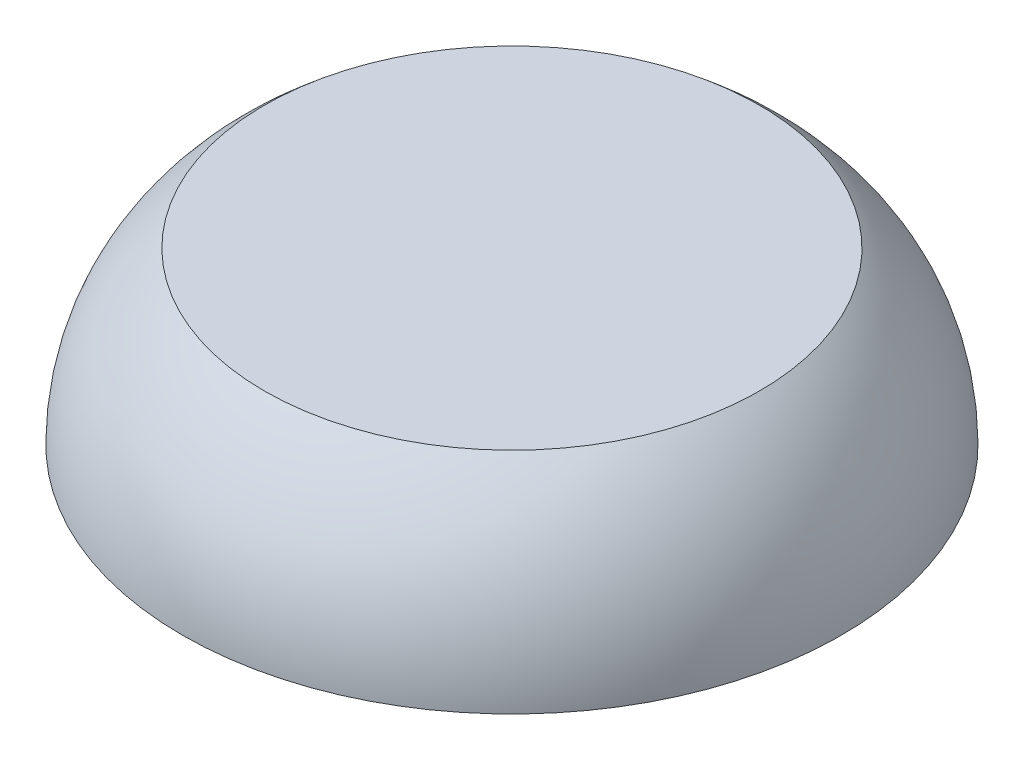
SolidWorks part; units mm, degrees
ref_plane "Front Plane" through (0, 0, 0) normal (0, 0, 1) x (1, 0, 0)
ref_plane "Top Plane" through (0, 0, 0) normal (0, 1, 0) x (1, 0, 0)
ref_plane "Right Plane" through (0, 0, 0) normal (1, 0, 0) x (0, 0, -1)
sketch "Sketch1" plane through (0, 0, 0) normal (0, 0, 1) x (1, 0, 0)
  line L0 (0, 0) -> (0, -11.3847) construction
  line L1 (2.1783, -5.9275) -> (0, -5.9275)
  line L2 (2.9, -7.4275) -> (0, -7.4275)
  line L3 (0, -5.9275) -> (0, -7.4275)
  arc A0 (2.9, -7.4275) -> (2.1783, -5.9275) centre (0.9803, -7.4275) ccw
  dimension "D2" = 1.9197
  dimension "D1" = 2.9
  dimension "D3" = 1.5
revolve "Revolve1" add sketch "Sketch1" angle 360 about L0
